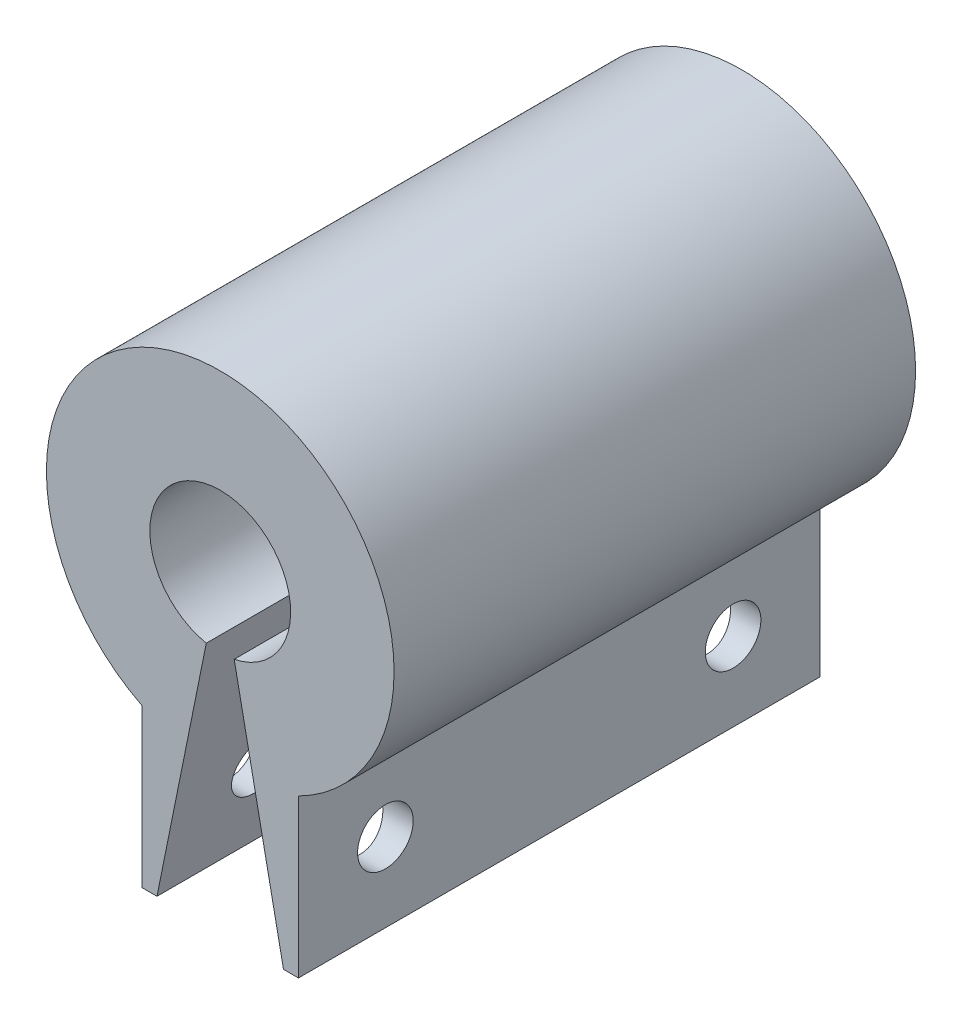
SolidWorks part; units mm, degrees
ref_plane "正面" through (0, 0, 0) normal (0, 0, 1) x (1, 0, 0)
ref_plane "平面" through (0, 0, 0) normal (0, 1, 0) x (1, 0, 0)
ref_plane "右側面" through (0, 0, 0) normal (1, 0, 0) x (0, 0, -1)
sketch "ｽｹｯﾁ1" plane through (0, 0, 0) normal (0, 0, 1) x (1, 0, 0)
  line L2 (-4.5, -8.9303) -> (-4.5, -18)
  line L3 (-4.5, -18) -> (4.5, -18)
  line L4 (4.5, -8.9303) -> (4.5, -18)
  arc A0 (4.5, -8.9303) -> (-4.5, -8.9303) centre (0, 0) ccw
  point P8 (0, -18)
  dimension "D1" = 20
  dimension "D2" = 9
  dimension "D3" = 18
extrude "ﾎﾞｽ - 押し出し1" add sketch "ｽｹｯﾁ1" along normal blind 30
sketch "ｽｹｯﾁ2" plane through (0, 0, 30) normal (0, 0, 1) x (1, 0, 0)
  circle A0 centre (0, 0) radius 4.05
  dimension "D1" = 8.1
extrude "ｶｯﾄ - 押し出し1" cut sketch "ｽｹｯﾁ2" against normal blind 15
sketch "ｽｹｯﾁ3" plane through (0, 0, 0) normal (0, 0, -1) x (-1, 0, 0)
  circle A0 centre (0, 0) radius 1.575
  dimension "D1" = 3.15
extrude "ｶｯﾄ - 押し出し2" cut sketch "ｽｹｯﾁ3" against normal blind 15
sketch "ｽｹｯﾁ4" plane through (0, 0, 30) normal (0, 0, 1) x (1, 0, 0)
  line L9 (-4.5, -18) -> (4.5, -18) construction
  line L10 (-0.3121, -1.5438) -> (-3.6388, -18)
  line L11 (0.3121, -1.5438) -> (3.6388, -18)
  arc A0 (-3.6388, -18) -> (3.6388, -18) centre (0, 0) ccw
  circle A1 centre (0, 0) radius 1.575 construction
  arc A2 (-0.3121, -1.5438) -> (0.3121, -1.5438) centre (0, 0) ccw
  point P5 (-0.3121, -1.5438)
  point P6 (0.3121, -1.5438)
  point P7 (0, -18.3641)
  dimension "D1" = 0.6283
sketch "ｽｹｯﾁ10" plane through (4.5, 0, 0) normal (1, 0, 0) x (0, 0, -1)
  line L0 (-30, -18) -> (-30, -8.9303) construction
  line L1 (0, -18) -> (0, -8.9303) construction
  circle A0 centre (-25, -13.4651) radius 1.6
  circle A1 centre (-5, -13.4651) radius 1.6
  point P9 (-30, -13.4651)
  dimension "D3" = 3.2
  dimension "D1" = 5
  dimension "D2" = 5
extrude "ｶｯﾄ - 押し出し8" cut sketch "ｽｹｯﾁ10" against normal through all
extrude "ｶｯﾄ - 押し出し9" cut sketch "ｽｹｯﾁ4" against normal through all
equation "\"D1@ｽｹｯﾁ4\"=2*PI*(3.15-3.05)"
